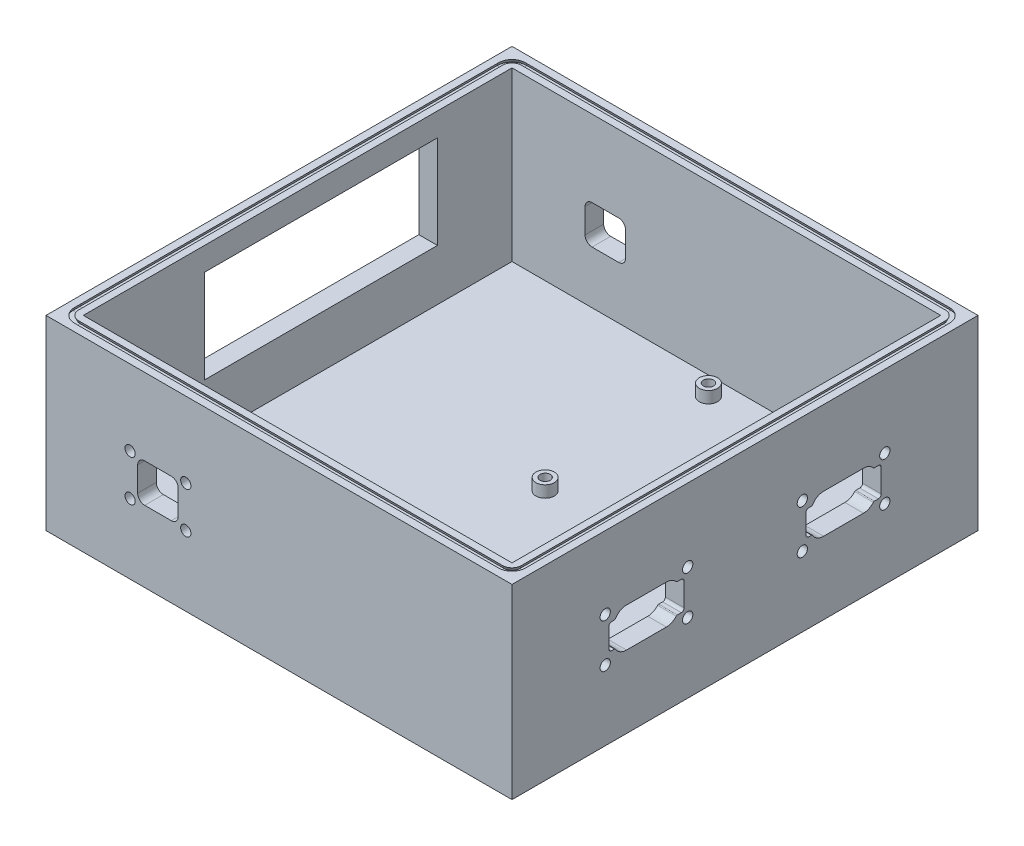
SolidWorks part; units mm, degrees
ref_plane "Front Plane" through (0, 0, 0) normal (0, 0, 1) x (1, 0, 0)
ref_plane "Top Plane" through (0, 0, 0) normal (0, 1, 0) x (1, 0, 0)
ref_plane "Right Plane" through (0, 0, 0) normal (1, 0, 0) x (0, 0, -1)
sketch "Sketch1" plane through (0, 0, 0) normal (0, 1, 0) x (1, 0, 0)
  line L1 (0, 0) -> (254, 0)
  line L2 (0, 0) -> (0, 254)
  line L3 (0, 254) -> (254, 254)
  line L4 (254, 0) -> (254, 254)
  dimension "D1" = 254
  dimension "D2" = 254
extrude "Boss-Extrude1" add sketch "Sketch1" along normal blind 101.6
sketch "12 pin hole" [suppressed] plane through (254, 0, 0) normal (1, 0, 0) x (0, 0, -1)
  line L8 (50.8, 10.16) -> (95.758, 10.16) construction
  line L9 (50.8, 10.16) -> (50.8, 34.036) construction
  line L10 (50.8, 34.036) -> (95.758, 34.036) construction
  line L11 (95.758, 10.16) -> (95.758, 34.036) construction
  line L12 (55.7357, 28.956) -> (54.2925, 28.956)
  line L13 (52.7685, 27.432) -> (52.7685, 16.764)
  line L14 (54.2925, 15.24) -> (55.7357, 15.24)
  line L16 (90.087, 29.972) -> (92.2655, 29.972)
  line L17 (93.7895, 28.448) -> (93.7895, 15.748)
  line L18 (92.2655, 14.224) -> (90.087, 14.224)
  line L21 (62.4205, 25.654) -> (84.1375, 25.654) construction
  line L22 (62.4205, 25.654) -> (62.4205, 18.542) construction
  line L23 (62.4205, 18.542) -> (84.1375, 18.542) construction
  line L24 (84.1375, 25.654) -> (84.1375, 18.542) construction
  line L25 (62.4205, 32.7152) -> (84.1375, 32.7152)
  line L26 (62.4205, 11.4808) -> (84.1375, 11.4808)
  line L27 (52.7685, 22.098) -> (50.8, 22.098) construction
  line L28 (93.7895, 22.098) -> (95.758, 22.098) construction
  arc A4 (62.4205, 32.7152) -> (56.3868, 29.3222) centre (62.4205, 25.654) ccw
  arc A5 (89.5075, 30.2392) -> (84.1375, 32.7152) centre (84.1375, 25.654) ccw
  arc A6 (62.4205, 11.4808) -> (56.3868, 14.8738) centre (62.4205, 18.542) cw
  arc A7 (89.5075, 13.9568) -> (84.1375, 11.4808) centre (84.1375, 18.542) cw
  arc A8 (90.087, 29.972) -> (89.5075, 30.2392) centre (90.087, 30.734) cw
  arc A9 (90.087, 14.224) -> (89.5075, 13.9568) centre (90.087, 13.462) ccw
  arc A10 (55.7357, 15.24) -> (56.3868, 14.8738) centre (55.7357, 14.478) cw
  arc A11 (55.7357, 28.956) -> (56.3868, 29.3222) centre (55.7357, 29.718) ccw
  arc A12 (92.2655, 29.972) -> (93.7895, 28.448) centre (92.2655, 28.448) cw
  arc A13 (93.7895, 15.748) -> (92.2655, 14.224) centre (92.2655, 15.748) cw
  arc A14 (52.7685, 16.764) -> (54.2925, 15.24) centre (54.2925, 16.764) ccw
  arc A15 (54.2925, 28.956) -> (52.7685, 27.432) centre (54.2925, 27.432) ccw
  point P25 (50.8, 22.098)
  point P28 (52.7685, 22.098)
  point P29 (93.7895, 22.098)
  point P34 (62.4205, 22.098)
  point P35 (84.1375, 22.098)
  point P44 (73.279, 10.16)
  point P46 (73.279, 11.4808)
  point P59 (93.7895, 29.972)
  point P62 (93.7895, 14.224)
  point P65 (52.7685, 15.24)
  point P68 (52.7685, 28.956)
  dimension "D4" = 41.021
  dimension "D5" = 15.748
  dimension "D11" = 7.0612
  dimension "D12" = 0.762
  dimension "D13" = 1.524
  dimension "D1" = 44.958
  dimension "D2" = 23.876
  dimension "D8" = 13.716
  dimension "D9" = 21.2344
  dimension "D10" = 21.717
sketch "Sketch2" plane through (0, 101.6, 0) normal (0, 1, 0) x (1, 0, 0)
  line L0 (0, 254) -> (0, 0) construction
  line L1 (10.16, 10.16) -> (243.84, 10.16)
  line L2 (10.16, 10.16) -> (10.16, 243.84)
  line L3 (10.16, 243.84) -> (243.84, 243.84)
  line L4 (243.84, 10.16) -> (243.84, 243.84)
  line L5 (254, 254) -> (0, 254) construction
  line L6 (254, 0) -> (254, 254) construction
  line L7 (0, 0) -> (254, 0) construction
  dimension "D1" = 10.16
  dimension "D2" = 10.16
  dimension "D3" = 10.16
  dimension "D4" = 10.16
extrude "Cut-Extrude1" cut sketch "Sketch2" against normal blind 91.44
ref_plane "Plane1" through (0, 101.6, 0) normal (0, 1, 0) x (1, 0, 0)
sketch "Sketch3" plane through (0, 101.6, 0) normal (0, 1, 0) x (1, 0, 0)
  line L4 (6.35, 11.43) -> (6.35, 242.57)
  line L5 (243.84, 243.84) -> (10.16, 243.84) construction
  line L6 (10.16, 243.84) -> (10.16, 10.16) construction
  line L7 (243.84, 10.16) -> (243.84, 243.84) construction
  line L8 (10.16, 10.16) -> (243.84, 10.16) construction
  line L13 (11.43, 247.65) -> (242.57, 247.65)
  line L14 (247.65, 242.57) -> (247.65, 11.43)
  line L15 (242.57, 6.35) -> (11.43, 6.35)
  arc A0 (6.35, 242.57) -> (11.43, 247.65) centre (11.43, 242.57) cw
  arc A1 (242.57, 247.65) -> (247.65, 242.57) centre (242.57, 242.57) cw
  arc A2 (247.65, 11.43) -> (242.57, 6.35) centre (242.57, 11.43) cw
  arc A3 (11.43, 6.35) -> (6.35, 11.43) centre (11.43, 11.43) cw
  dimension "D5" = 5.08
  dimension "D1" = 3.81
  dimension "D2" = 3.81
  dimension "D3" = 3.81
  dimension "D4" = 3.81
ref_plane "Plane2" through (0, 0, 0) normal (0, 0, 1) x (1, 0, 0)
ref_plane "Plane3" through (0, 0, -15.24) normal (0, 0, 1) x (1, 0, 0)
sketch "Sketch4" plane through (0, 0, -15.24) normal (0, 0, 1) x (1, 0, 0)
  line L0 (4.064, 101.6) -> (3.2724, 99.822)
  line L1 (6.35, 101.6) -> (7.1416, 99.822)
  line L2 (3.2724, 99.822) -> (7.1416, 99.822)
  line L5 (4.064, 101.6) -> (6.35, 101.6)
  dimension "D1" = 1.778
  dimension "D2" = 2.286
  dimension "D3" = 66
  dimension "D4" = 66
sweep "Cut-Sweep2" cut profiles "Sketch4" path "Sketch3"
sketch "Sketch13" plane through (254, 0, 0) normal (1, 0, 0) x (0, 0, -1)
  line L0 (50.8, 38.1) -> (50.8, 0) construction
  line L1 (0, 0) -> (254, 0) construction
  line L2 (50.8, 38.1) -> (0, 38.1) construction
  line L3 (0, 101.6) -> (0, 0) construction
  line L4 (203.2, 0) -> (203.2, 38.1) construction
  line L5 (203.2, 38.1) -> (254, 38.1) construction
  line L6 (254, 101.6) -> (254, 0) construction
  line B0 (50.8, 38.1) -> (95.758, 38.1) construction
  line B1 (50.8, 38.1) -> (50.8, 61.976) construction
  line B2 (50.8, 61.976) -> (95.758, 61.976) construction
  line B3 (95.758, 38.1) -> (95.758, 61.976) construction
  line B4 (55.7357, 56.896) -> (54.2925, 56.896)
  line B5 (52.7685, 55.372) -> (52.7685, 44.704)
  line B6 (54.2925, 43.18) -> (55.7357, 43.18)
  line B7 (90.087, 57.912) -> (92.2655, 57.912)
  line B8 (93.7895, 56.388) -> (93.7895, 43.688)
  line B9 (92.2655, 42.164) -> (90.087, 42.164)
  line B10 (62.4205, 60.6552) -> (84.1375, 60.6552)
  line B11 (62.4205, 39.4208) -> (84.1375, 39.4208)
  arc B12 (62.4205, 60.6552) -> (56.3868, 57.2622) centre (62.4205, 53.594) ccw
  arc B13 (89.5075, 58.1792) -> (84.1375, 60.6552) centre (84.1375, 53.594) ccw
  arc B14 (62.4205, 39.4208) -> (56.3868, 42.8138) centre (62.4205, 46.482) cw
  arc B15 (89.5075, 41.8968) -> (84.1375, 39.4208) centre (84.1375, 46.482) cw
  arc B16 (90.087, 57.912) -> (89.5075, 58.1792) centre (90.087, 58.674) cw
  arc B17 (90.087, 42.164) -> (89.5075, 41.8968) centre (90.087, 41.402) ccw
  arc B18 (55.7357, 43.18) -> (56.3868, 42.8138) centre (55.7357, 42.418) cw
  arc B19 (55.7357, 56.896) -> (56.3868, 57.2622) centre (55.7357, 57.658) ccw
  arc B20 (92.2655, 57.912) -> (93.7895, 56.388) centre (92.2655, 56.388) cw
  arc B21 (93.7895, 43.688) -> (92.2655, 42.164) centre (92.2655, 43.688) cw
  arc B22 (52.7685, 44.704) -> (54.2925, 43.18) centre (54.2925, 44.704) ccw
  arc B23 (54.2925, 56.896) -> (52.7685, 55.372) centre (54.2925, 55.372) ccw
  line B24 (158.242, 38.1) -> (203.2, 38.1) construction
  line B25 (158.242, 38.1) -> (158.242, 61.976) construction
  line B26 (158.242, 61.976) -> (203.2, 61.976) construction
  line B27 (203.2, 38.1) -> (203.2, 61.976) construction
  line B28 (163.1777, 56.896) -> (161.7345, 56.896)
  line B29 (160.2105, 55.372) -> (160.2105, 44.704)
  line B30 (161.7345, 43.18) -> (163.1777, 43.18)
  line B31 (197.529, 57.912) -> (199.7075, 57.912)
  line B32 (201.2315, 56.388) -> (201.2315, 43.688)
  line B33 (199.7075, 42.164) -> (197.529, 42.164)
  line B34 (169.8625, 60.6552) -> (191.5795, 60.6552)
  line B35 (169.8625, 39.4208) -> (191.5795, 39.4208)
  arc B36 (169.8625, 60.6552) -> (163.8288, 57.2622) centre (169.8625, 53.594) ccw
  arc B37 (196.9495, 58.1792) -> (191.5795, 60.6552) centre (191.5795, 53.594) ccw
  arc B38 (169.8625, 39.4208) -> (163.8288, 42.8138) centre (169.8625, 46.482) cw
  arc B39 (196.9495, 41.8968) -> (191.5795, 39.4208) centre (191.5795, 46.482) cw
  arc B40 (197.529, 57.912) -> (196.9495, 58.1792) centre (197.529, 58.674) cw
  arc B41 (197.529, 42.164) -> (196.9495, 41.8968) centre (197.529, 41.402) ccw
  arc B42 (163.1777, 43.18) -> (163.8288, 42.8138) centre (163.1777, 42.418) cw
  arc B43 (163.1777, 56.896) -> (163.8288, 57.2622) centre (163.1777, 57.658) ccw
  arc B44 (199.7075, 57.912) -> (201.2315, 56.388) centre (199.7075, 56.388) cw
  arc B45 (201.2315, 43.688) -> (199.7075, 42.164) centre (199.7075, 43.688) cw
  arc B46 (160.2105, 44.704) -> (161.7345, 43.18) centre (161.7345, 44.704) ccw
  arc B47 (161.7345, 56.896) -> (160.2105, 55.372) centre (161.7345, 55.372) ccw
  dimension "D1" = 50.8
  dimension "D2" = 38.1
sketch_block_instance "Block7-3"
sketch_block "Block7" parameters "D6"=7.0612, "D7"=0.762, "D8"=1.524, "D1"=44.958, "D2"=23.876, "D3"=41.021, "D4"=21.2344, "D5"=21.717
sketch_block_instance "Block7-4"
extrude "Cut-Extrude10" cut sketch "Sketch13" against normal up to next
sketch "12 pin mount" plane through (254, 0, 0) normal (1, 0, 0) x (0, 0, -1)
  circle A0 centre (95.758, 61.976) radius 2.8
  circle A1 centre (95.758, 38.1) radius 2.8
  circle A2 centre (50.8, 38.1) radius 2.8
  circle A3 centre (50.8, 61.976) radius 2.8
  circle A4 centre (158.242, 61.976) radius 2.8
  circle A5 centre (203.2, 61.976) radius 2.8
  circle A6 centre (203.2, 38.1) radius 2.8
  circle A7 centre (158.242, 38.1) radius 2.8
  dimension "D1" = 5.6
extrude "Cut-Extrude3" cut sketch "12 pin mount" against normal blind 5.5
sketch "4 pin connector" plane through (0, 0, 0) normal (0, 0, 1) x (1, 0, 0)
  line L0 (76.2, 0) -> (76.2, 38.1) construction
  line L1 (0, 0) -> (254, 0) construction
  line L2 (76.2, 38.1) -> (254, 38.1) construction
  line L3 (254, 101.6) -> (254, 0) construction
  line L5 (45.847, 60.5536) -> (76.2, 60.5536) construction
  line L6 (45.847, 60.5536) -> (45.847, 38.1) construction
  line L7 (45.847, 38.1) -> (76.2, 38.1) construction
  line L8 (76.2, 60.5536) -> (76.2, 38.1) construction
  line L9 (53.7845, 59.817) -> (68.2625, 59.817)
  line L10 (49.9745, 56.007) -> (49.9745, 42.6466)
  line L11 (53.7845, 38.8366) -> (68.2625, 38.8366)
  line L12 (72.0725, 56.007) -> (72.0725, 42.6466)
  line L13 (61.0235, 38.8366) -> (61.0235, 59.817) construction
  line L14 (49.9745, 49.3268) -> (72.0725, 49.3268) construction
  arc A0 (68.2625, 59.817) -> (72.0725, 56.007) centre (68.2625, 56.007) cw
  arc A1 (68.2625, 38.8366) -> (72.0725, 42.6466) centre (68.2625, 42.6466) ccw
  arc A2 (49.9745, 42.6466) -> (53.7845, 38.8366) centre (53.7845, 42.6466) ccw
  arc A3 (53.7845, 59.817) -> (49.9745, 56.007) centre (53.7845, 56.007) ccw
  point P4 (61.0235, 49.3268)
  point P12 (61.0235, 38.1)
  point P15 (76.2, 49.3268)
  point P20 (72.0725, 59.817)
  point P24 (72.0725, 38.8366)
  point P29 (49.9745, 59.817)
  dimension "D1" = 22.098
  dimension "D7" = 3.81
  dimension "D2" = 22.4536
  dimension "D3" = 30.353
  dimension "D4" = 38.1
  dimension "D5" = 177.8
  dimension "D6" = 20.9804
extrude "Cut-Extrude5" cut sketch "4 pin connector" against normal up to next
extrude "Cut-Extrude6" cut sketch "Sketch5<2>" along normal up to next from surface starting at face at (127, 50.8, -254)
sketch "Sketch5<2>" plane through (0, 0, 0) normal (0, 0, 1) x (1, 0, 0) same geometry as "4 pin connector"
sketch "Sketch6" plane through (0, 0, 0) normal (0, 0, 1) x (1, 0, 0)
  circle A0 centre (76.2, 60.5536) radius 2.8
  circle A1 centre (76.2, 38.1) radius 2.8
  circle A2 centre (45.847, 38.1) radius 2.8
  circle A3 centre (45.847, 60.5536) radius 2.8
  dimension "D1" = 5.6
extrude "Cut-Extrude7" cut sketch "Sketch6" against normal blind 5.5
extrude "Cut-Extrude8" cut sketch "Sketch6<2>" along normal blind 5.5 from surface starting at face at (61.0235, 49.3268, -254)
sketch "Sketch6<2>" plane through (0, 0, 0) normal (0, 0, 1) x (1, 0, 0) same geometry as "Sketch6"
sketch "Sketch7" plane through (0, 10.16, 0) normal (0, 1, 0) x (1, 0, 0)
  line L0 (193.04, 189.1889) -> (243.84, 189.1889) construction
  line L1 (243.84, 10.16) -> (243.84, 243.84) construction
  line L5 (193.04, 144.6739) -> (127.38, 144.6739) construction
  line L6 (193.04, 144.6739) -> (193.04, 233.7039) construction
  line L7 (193.04, 233.7039) -> (127.38, 233.7039) construction
  line L8 (127.38, 144.6739) -> (127.38, 233.7039) construction
  circle A0 centre (127.38, 144.6739) radius 5
  circle A1 centre (193.04, 144.6739) radius 5
  circle A2 centre (193.04, 233.7039) radius 5
  circle A3 centre (127.38, 233.7039) radius 5
  dimension "D1" = 10
  dimension "D2" = 89.03
  dimension "D3" = 65.66
  dimension "D4" = 50.8
sketch "Sketch8" plane through (0, 10.16, 0) normal (0, 1, 0) x (1, 0, 0)
  circle A0 centre (127.38, 233.7039) radius 2.8
  circle A1 centre (193.04, 233.7039) radius 2.8
  circle A2 centre (193.04, 144.6739) radius 2.8
  circle A3 centre (127.38, 144.6739) radius 2.8
  dimension "D1" = 5.6
extrude "Boss-Extrude2" add sketch "Sketch7" along normal blind 6.35
extrude "Cut-Extrude9" cut sketch "Sketch8" against normal blind 5.5 from surface starting at face at (193.04, 16.51, -139.6739)
sketch "Sketch14" plane through (0, 0, 0) normal (-1, 0, 0) x (0, 0, 1)
  line L0 (-254, 101.6) -> (-254, 0) construction
  line L1 (-203.2, 88.9) -> (-76.2, 88.9)
  line L2 (-203.2, 88.9) -> (-203.2, 38.1)
  line L3 (-203.2, 38.1) -> (-76.2, 38.1)
  line L4 (-76.2, 88.9) -> (-76.2, 38.1)
  line L5 (-254, 0) -> (0, 0) construction
  point P6 (-76.2, 63.5)
  point P9 (0, 0)
  dimension "D1" = 177.8
  dimension "D2" = 50.8
  dimension "D3" = 50.8
  dimension "D4" = 38.1
extrude "Cut-Extrude11" cut sketch "Sketch14" against normal up to next
equation "\"M4 insert  width\"= 5.6mm"
equation "\"M4 insert  depth\"= 5.5mm"
equation "\"depth\"=0.1"
